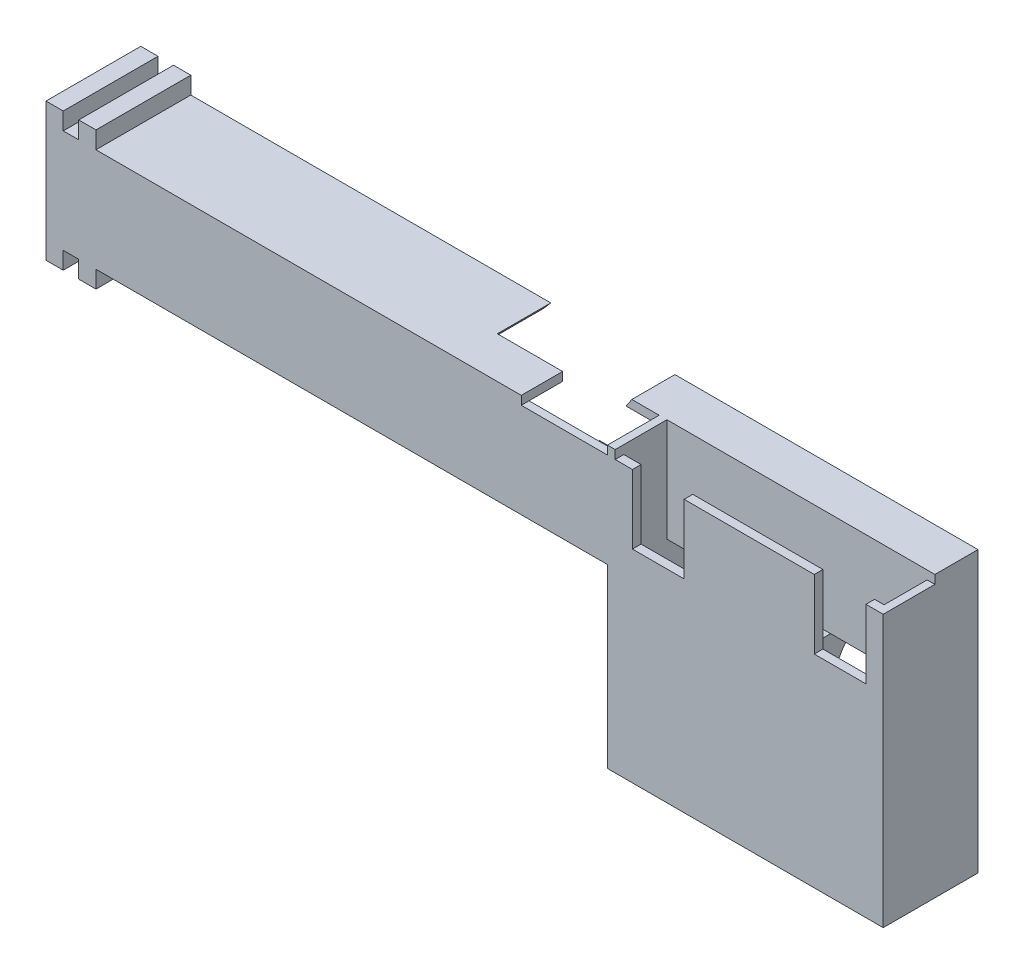
SolidWorks part; units mm, degrees
ref_plane "Front Plane" through (0, 0, 0) normal (0, 0, 1) x (1, 0, 0)
ref_plane "Top Plane" through (0, 0, 0) normal (0, 1, 0) x (1, 0, 0)
ref_plane "Right Plane" through (0, 0, 0) normal (1, 0, 0) x (0, 0, -1)
sketch "Sketch1" plane through (0, 0, 0) normal (0, 0, 1) x (1, 0, 0)
  line L3 (0, 20.5) -> (32, 20.5)
  line L4 (0.9, 20.5) -> (0.9, 31.5)
  line L5 (31.1, 20.5) -> (31.1, 31.5)
  line L6 (0.9, 31.5) -> (31.1, 31.5)
  line L7 (0.9, 20.5) -> (0.9, 6)
  line L8 (31.1, 20.5) -> (31.1, 6)
  line L9 (0.9, 6) -> (31.1, 6)
  line L10 (0, 20.5) -> (0, 0)
  line L11 (0, 0) -> (32, 0)
  line L12 (32, 0) -> (32, 20.5)
  line L13 (0, 20.5) -> (0, 31.5)
  line L14 (0, 31.5) -> (0.9, 31.5)
  line L15 (0, 31.5) -> (0.9, 31.5)
  line L16 (32, 20.5) -> (32, 31.5)
  line L17 (32, 31.5) -> (31.1, 31.5)
  line L21 (0, 31.5) -> (0.9, 31.5)
  line L22 (31.1, 31.5) -> (32, 31.5)
  line L31 (0, 31.5) -> (32, 31.5)
  line L41 (12.1, 20.5) -> (19.9, 20.5)
  line L42 (12.1, 20.5) -> (12.1, 6)
  line L43 (12.1, 6) -> (19.9, 6)
  line L44 (19.9, 20.5) -> (19.9, 6)
  point P0 (0, 0)
  point P11 (0, 20.5)
  point P32 (16, 6)
  point P40 (16, 20.5)
  dimension "D2" = 6
  dimension "D3" = 0.9
  dimension "D6" = 11
  dimension "D7" = 14.5
  dimension "D8" = 0.9
  dimension "D9" = 32
  dimension "D18" = 7.8
  dimension "D19" = 3.9
extrude "Boss-Extrude2" add sketch "Sketch1<3>" along normal blind 11 contours L11 L12 L3 L8 L9 L7 L10 | L14 L13 L3 L4 | L16 L17 L5 L3 | L4 L14 L13 region at (0.45, 26, 0) region at (16, 4.2266, 0) region at (31.55, 26, 0)
sketch "Sketch1<3>" plane through (0, 0, 0) normal (0, 0, 1) x (1, 0, 0) same geometry as "Sketch1"
extrude "Boss-Extrude3" add sketch "Sketch1<4>" along normal blind 5 contours L6 L4 L3 L5 region at (16, 26, 0)
sketch "Sketch1<4>" plane through (0, 0, 0) normal (0, 0, 1) x (1, 0, 0) same geometry as "Sketch1"
sketch "Sketch2" plane through (0, 6, 0) normal (0, 1, 0) x (1, 0, 0)
  line L0 (0.9, -11) -> (0.9, -10)
  line L1 (0.9, -11) -> (0.9, -5) construction
  line L2 (31.1, -11) -> (31.1, -10)
  line L3 (31.1, -11) -> (31.1, 0) construction
  line L4 (0.9, -10) -> (31.1, -10)
  line L5 (0.9, -11) -> (31.1, -11)
  dimension "D1" = 1
extrude "Boss-Extrude4" add sketch "Sketch2" along normal blind 25.5
extrude "Boss-Extrude5" add sketch "Sketch1" along normal blind 11 contours L44 L3 L42 L9 region at (16, 13.25, 0)
sketch "Sketch3" plane through (0, 0, 10) normal (0, 0, -1) x (-1, 0, 0)
  line L0 (-12.1, 6) -> (-12.1, 20.5) construction
  line L1 (-0.9, 6) -> (-12.1, 6)
  line L2 (-0.9, 6) -> (-0.9, 17)
  line L3 (-0.9, 17) -> (-12.1, 17)
  line L4 (-12.1, 6) -> (-12.1, 17)
  line L5 (-19.9, 6) -> (-19.9, 20.5) construction
  line L6 (-31.1, 6) -> (-19.9, 6)
  line L7 (-31.1, 6) -> (-31.1, 17)
  line L8 (-31.1, 17) -> (-19.9, 17)
  line L9 (-19.9, 6) -> (-19.9, 17)
  dimension "D1" = 11
  dimension "D2" = 11
extrude "Boss-Extrude6" add sketch "Sketch3" along normal blind 5
sketch "Sketch4" plane through (0, 31.5, 0) normal (0, 1, 0) x (1, 0, 0)
  line L0 (0, 0) -> (32, 0) construction
  line L1 (0, -0.4) -> (31.1, -0.4)
  line L2 (0, -0.4) -> (0, -4.4)
  line L3 (0, -4.4) -> (31.1, -4.4)
  line L4 (31.1, -0.4) -> (31.1, -4.4)
  line L6 (31.1, -10) -> (31.1, -5) construction
  line L8 (0, -11) -> (0, 0) construction
  dimension "D1" = 0.4
  dimension "D2" = 4
extrude "Cut-Extrude1" cut sketch "Sketch4" against normal blind 10
sketch "Sketch5" plane through (0, 31.5, 0) normal (0, 1, 0) x (1, 0, 0)
  line L0 (0, -11) -> (0, -4.4) construction
  line L1 (32, 0) -> (0, 0)
  line L2 (32, 0) -> (32, -5)
  line L3 (32, -5) -> (0, -5)
  line L4 (0, 0) -> (0, -5)
  line L5 (0.9, -5) -> (31.1, -5) construction
extrude "Boss-Extrude7" add sketch "Sketch5" along normal blind 1
sketch "Sketch7" plane through (0, 0, 0) normal (-1, 0, 0) x (0, 0, 1)
  line L0 (0, 32.5) -> (0, 0) construction
  line L1 (5, 32.5) -> (0, 32.5)
  line L2 (5, 32.5) -> (5, 31.5)
  line L3 (5, 31.5) -> (0, 31.5)
  line L4 (0, 32.5) -> (0, 31.5)
  line L5 (11, 31.5) -> (5, 31.5) construction
  line L6 (4.4, 21.5) -> (4.4, 31.5) construction
  line L7 (0, 21.5) -> (5, 21.5)
  line L8 (0, 21.5) -> (0, 20.4962)
  line L9 (0, 20.4962) -> (5, 20.4962)
  line L10 (5, 21.5) -> (5, 20.4962)
  line L11 (5, 31.5) -> (5, 21.5)
  line L12 (4.4, 31.5) -> (4.4, 21.5)
  line M5 (0.4, 31.5) -> (4.4, 31.5)
  line M7 (4.4, 21.5) -> (0.4, 21.5)
  line M10 (5, 31.5) -> (5, 32.5)
  line M11 (5, 32.5) -> (0, 32.5)
  line M12 (0, 32.5) -> (0, 0)
  dimension "D1" = 1.0038
  dimension "D2" = 5
extrude "Boss-Extrude8" add sketch "Sketch7" along normal blind 62.24 contours L10 L7 L9 M7 M12 | L3 M10 M11 M12 M5 region at (0, 32, 2.5) region at (0, 20.9981, 2.5)
sketch "Sketch8" plane through (0, 0, 5) normal (0, 0, 1) x (1, 0, 0)
  line L0 (-62.24, 32.5) -> (32, 32.5) construction
  line L1 (0.9, 31.5) -> (0, 31.5)
  line L2 (0.9, 31.5) -> (0.9, 32.5)
  line L3 (0.9, 32.5) -> (0, 32.5)
  line L4 (0, 31.5) -> (0, 32.5)
  line L5 (0, 31.5) -> (0, 0) construction
extrude "Boss-Extrude9" add sketch "Sketch8" along normal blind 6
sketch "Sketch9" plane through (0, 0, 0) normal (-1, 0, 0) x (0, 0, 1)
  line L0 (11, 32.5) -> (11, 0) construction
  line L3 (11, 31.5) -> (5, 31.5)
  line L5 (5, 20.4962) -> (11, 20.4962)
  line L6 (5, 20.4962) -> (5, 21.4995)
  line L7 (5, 21.4995) -> (11, 21.4995)
  line L8 (11, 20.4962) -> (11, 21.4995)
  line L10 (11, 31.5) -> (10.1, 31.5)
  line L11 (11, 31.5) -> (11, 21.4995)
  line L12 (11, 21.4995) -> (10.1, 21.4995)
  line L13 (10.1, 31.5) -> (10.1, 21.4995)
  line M1 (11, 0) -> (11, 32.5)
  line M7 (5, 21.5) -> (5, 20.4962)
  dimension "D1" = 1.0033
  dimension "D2" = 0.9
extrude "Boss-Extrude10" add sketch "Sketch9" along normal blind 62.26 contours L7 L5 M7 M1 | L3 L13 L7 M1 region at (0, 26.4998, 10.55) region at (0, 20.9978, 8)
sketch "Sketch10" plane through (0, 0, 5) normal (0, 0, 1) x (1, 0, 0)
  line L0 (-62.24, 32.5) -> (0, 32.5) construction
  line L1 (-10, 32.5) -> (-62.24, 32.5)
  line L2 (-10, 32.5) -> (-10, 31.5)
  line L3 (-10, 31.5) -> (-62.24, 31.5)
  line L4 (-62.24, 32.5) -> (-62.24, 31.5)
  dimension "D1" = 10
extrude "Boss-Extrude11" add sketch "Sketch10" along normal blind 6
sketch "Sketch11" plane through (0, 0, 0) normal (0, 0, -1) x (-1, 0, 0)
  circle A0 centre (71.2419, 77.6773) radius 81.7
  circle A1 centre (71.2419, 77.6773) radius 70.15
  point P0 (71.2419, 77.6773)
  dimension "D3" = 163.4
  dimension "D4" = 140.3
  dimension "D1" = 129.2
  dimension "D2" = 105.4
extrude "Cut-Extrude2" cut sketch "Sketch11" against normal blind 6.2
sketch "Sketch12" plane through (-62.24, 0, 0) normal (-1, 0, 0) x (0, 0, 1)
  line L0 (11, 31.5) -> (11, 21.5)
  line L1 (0, 21.5) -> (11, 21.5)
  line L2 (0, 21.5) -> (0, 20.4962)
  line L3 (0, 20.4962) -> (11, 20.4962)
  line L4 (11, 21.5) -> (11, 20.4962)
  line L5 (0, 32.5) -> (11, 32.5)
  line L6 (0, 32.5) -> (0, 31.5)
  line L7 (0, 31.5) -> (11, 31.5)
  line L8 (11, 32.5) -> (11, 31.5)
  line L9 (10.1, 31.5) -> (11, 31.5)
  line L10 (10.1, 31.5) -> (10.1, 21.5)
  line L11 (10.1, 21.5) -> (11, 21.5)
  line L12 (11, 31.5) -> (11, 21.5)
  line L14 (11, 20.4962) -> (11, 31.5) construction
  line M5 (5, 21.4995) -> (5, 21.5)
  line M6 (5, 21.5) -> (0, 21.5)
  line M7 (0, 21.5) -> (0, 20.4962)
  line M8 (0, 20.4962) -> (5, 20.4962)
  line M9 (5, 20.4962) -> (5, 21.4995)
  dimension "D1" = 11
  dimension "D2" = 1.0038
  dimension "D3" = 1
  dimension "D4" = 0.9
extrude "Boss-Extrude12" add sketch "Sketch12" along normal blind 2.91 contours L8 L5 L6 L7 | L7 L10 L1 L0 | L4 L1 L3 M5 M9 | M9 M5 M6 M7 M8 region at (-62.24, 26.5, 10.55) region at (-62.24, 32, 5.5) region at (-62.24, 20.9981, 8) region at (-62.24, 20.9981, 2.5)
sketch "Sketch14" plane through (0, 20.4962, 0) normal (0, -1, 0) x (-1, 0, 0)
  line L0 (65.15, 0) -> (30.6051, 0) construction
  line L1 (65.15, -11) -> (63.15, -11)
  line L2 (65.15, -11) -> (65.15, 0)
  line L3 (65.15, 0) -> (63.15, 0)
  line L4 (63.15, -11) -> (63.15, 0)
  line L5 (65.15, -11) -> (0, -11) construction
  line L6 (59.35, 0) -> (61.35, 0)
  line L7 (59.35, 0) -> (59.35, -11)
  line L8 (59.35, -11) -> (61.35, -11)
  line L9 (61.35, 0) -> (61.35, -11)
  dimension "D1" = 2
  dimension "D2" = 2
  dimension "D3" = 1.8
extrude "Boss-Extrude13" add sketch "Sketch14" along normal blind 2
sketch "Sketch15" plane through (0, 32.5, 0) normal (0, 1, 0) x (1, 0, 0)
  line L0 (-10, -11) -> (-65.15, -11) construction
  line L1 (-65.15, 0) -> (-63.15, 0)
  line L2 (-65.15, 0) -> (-65.15, -11)
  line L3 (-65.15, -11) -> (-63.15, -11)
  line L4 (-63.15, 0) -> (-63.15, -11)
  line L5 (-61.35, 0) -> (-59.35, 0)
  line L6 (-61.35, 0) -> (-61.35, -11)
  line L7 (-61.35, -11) -> (-59.35, -11)
  line L8 (-59.35, 0) -> (-59.35, -11)
  dimension "D1" = 2
extrude "Boss-Extrude14" add sketch "Sketch15" along normal blind 2
sketch "Sketch20" plane through (19.9, 0, 0) normal (1, 0, 0) x (0, 0, -1)
  line L0 (0, 20.5) -> (0, 6) construction
  line L1 (-5, 6) -> (-5, 17) construction
  ellipse E0 centre (0, 13.25) end of major axis (0, 6) minor radius 5
  dimension "D1" = 7.25
  dimension "D2" = 10
extrude "Cut-Extrude3" cut sketch "Sketch20" against normal blind 10
sketch "Sketch21" plane through (0, 0, 11) normal (0, 0, 1) x (1, 0, 0)
  line L0 (32, 31.5) -> (0.9, 31.5) construction
  line L1 (2.9, 31.5) -> (8.9, 31.5)
  line L2 (2.9, 31.5) -> (2.9, 23.5)
  line L3 (2.9, 23.5) -> (8.9, 23.5)
  line L4 (8.9, 31.5) -> (8.9, 23.5)
  line L6 (24, 31.5) -> (30, 31.5)
  line L7 (24, 31.5) -> (24, 23.5)
  line L8 (24, 23.5) -> (30, 23.5)
  line L9 (30, 31.5) -> (30, 23.5)
  dimension "D1" = 2
  dimension "D2" = 2
  dimension "D3" = 6
  dimension "D4" = 6
  dimension "D5" = 8
  dimension "D6" = 8
extrude "Cut-Extrude4" cut sketch "Sketch21" against normal blind 1
